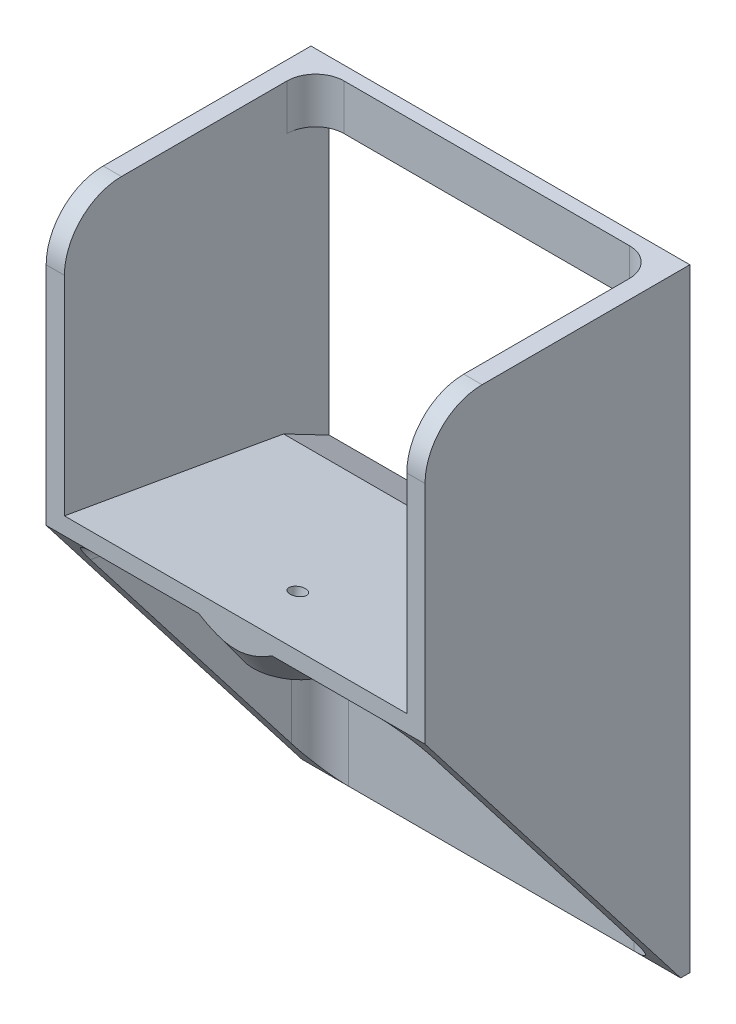
SolidWorks part; units mm, degrees
ref_plane "Front Plane" through (0, 0, 0) normal (0, 0, 1) x (1, 0, 0)
ref_plane "Top Plane" through (0, 0, 0) normal (0, 1, 0) x (1, 0, 0)
ref_plane "Right Plane" through (0, 0, 0) normal (1, 0, 0) x (0, 0, -1)
sketch "Sketch1" plane through (0, 0, 0) normal (1, 0, 0) x (0, 0, -1)
  line L0 (0, 0) -> (0, 50)
  line L1 (0, 50) -> (-8, 54.1748)
  line L2 (-8, 54.1748) -> (-46.4142, 60.9482)
  line L3 (0, 0) -> (-1.6, 0)
  line L4 (-1.6, 0) -> (-1.6, 50)
  line L8 (0, 50) -> (-1.6, 50) construction
  line L9 (-1328.2467, 50) -> (48671.7533, 50) construction
  line L10 (-1.6, 50) -> (-46.4142, 57.902)
  line L12 (-34.4683, 99.4589) -> (0, 93.3812) construction
  line L13 (-34.4683, 99.4589) -> (-41.4142, 60.0666) construction
  line L14 (0, 93.3812) -> (-6.9459, 53.9889) construction
  line L15 (-41.4142, 60.0666) -> (-6.9459, 53.9889) construction
  line L16 (-3.473, 73.6851) -> (-37.9412, 79.7628) construction
  line L17 (-17.2341, 96.4201) -> (-24.1801, 57.0278) construction
  line L18 (-1036.6595, 107.4589) -> (48963.3405, 107.4589) construction
  line L19 (-46.4142, 60.9482) -> (-46.4142, 57.902)
  point P3 (-8, 57.08)
  point P9 (-20.7071, 76.7239)
  dimension "D1" = 1.6
  dimension "D2" = 8
  dimension "D3" = 35
  dimension "D4" = 50
  dimension "D5" = 8
  dimension "D6" = 40
  dimension "D7" = 10
  dimension "D8" = 3
  dimension "D9" = 5
extrude "Boss-Extrude1" add sketch "Sketch1" along normal blind 30 and the other way blind 30 contours L2 L19 L10 L4 L3 L0 L1 region at (0, 0.7661, 0.8)
sketch "Sketch2" plane through (30, 0, 0) normal (1, 0, 0) x (0, 0, -1)
  line L0 (0, 0) -> (0, 107.4589)
  line L1 (0, 107.4589) -> (-46.4142, 107.4589)
  line L2 (-46.4142, 107.4589) -> (-46.4142, 57.902)
  line L3 (-46.4142, 57.902) -> (-1.6, 0)
  line L4 (-1.6, 0) -> (0, 0)
  line L5 (-201036.6595, 107.4589) -> (248963.3405, 107.4589) construction
extrude "Boss-Extrude2" add sketch "Sketch2" along normal blind 3.2
mirror "Mirror1" about plane through (0, 0, 0) normal (1, 0, 0) of "Boss-Extrude2"
sketch "Sketch3" plane through (0, 51.1731, -9.0232) normal (0, 0.9848, -0.1736) x (1, 0, 0)
  line L0 (0, -17.2858) -> (0, -56.2926) construction
  circle A0 centre (0, -45.2155) radius 1.35
  point P2 (0, 0)
  point P6 (0, 0)
  dimension "D1" = 2.7
  dimension "D2" = 6
extrude "Cut-Extrude1" cut sketch "Sketch3" against normal through all
sketch "Sketch4" plane through (0, 48.2187, -8.5023) normal (0, -0.9848, 0.1736) x (1, 0, 0)
  circle A0 centre (0, 45.2155) radius 6.35
  circle A1 centre (0, 45.2155) radius 1.35
  circle A2 centre (0, 45.2155) radius 1.35
  dimension "D1" = 0
  dimension "D2" = 5
extrude "Boss-Extrude3" add sketch "Sketch4" along normal blind 6
chamfer "Chamfer1" distance 6 angle 45 1 edges at (0, 57.173, 42.2798)
fillet "Fillet1" radius 5 5 edges at (-30, 53.951, 24.0071) (-30, 25, 1.6) (0, 50, 1.6) (30, 25, 1.6) (30, 53.951, 24.0071)
sketch "Sketch5" plane through (30, 0, 0) normal (-1, 0, 0) x (0, 0, 1)
  line L0 (201036.6595, 107.4589) -> (-248963.3405, 107.4589) construction
  line L1 (0, 107.4589) -> (2.4, 107.4589)
  line L2 (0, 107.4589) -> (0, 99.4589)
  line L3 (0, 99.4589) -> (2.4, 99.4589)
  line L4 (2.4, 107.4589) -> (2.4, 99.4589)
  line L5 (1.2, 99.4589) -> (1.2, 107.4589) construction
  line L6 (0, 103.4589) -> (2.4, 103.4589) construction
  line L7 (0, 0) -> (0, 50) construction
  point P4 (0, 0)
  point P7 (0, 0)
  point P352 (1.2, 103.4589)
  dimension "D1" = 2.4
  dimension "D2" = 8
extrude "Boss-Extrude4" add sketch "Sketch5" along normal up to surface (60 mm away) up to face at (-30, 76.0082, 20.1657)
fillet "Fillet2" radius 5 2 edges at (-30, 103.4589, 2.4) (30, 103.4589, 2.4)
fillet "Fillet3" radius 10 2 edges at (-31.6, 107.4589, 46.4142) (31.6, 107.4589, 46.4142)
equation "\"D1@Chamfer1\"=\"D1@Boss-Extrude3\""
